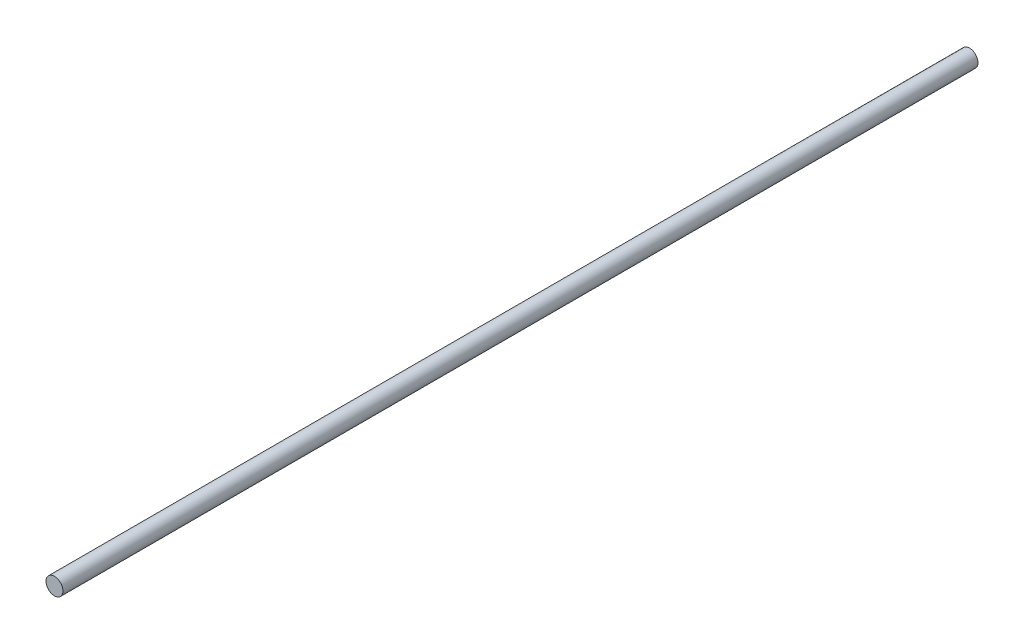
SolidWorks part; units mm, degrees
ref_plane "Front Plane" through (0, 0, 0) normal (0, 0, 1) x (1, 0, 0)
ref_plane "Top Plane" through (0, 0, 0) normal (0, 1, 0) x (1, 0, 0)
ref_plane "Right Plane" through (0, 0, 0) normal (1, 0, 0) x (0, 0, -1)
sketch "Sketch1" plane through (0, 0, 0) normal (0, 0, 1) x (1, 0, 0)
  circle A0 centre (0, 0) radius 4
extrude "Extrude2" add sketch "Sketch1" along normal blind 215.5 and the other way blind 215.5
